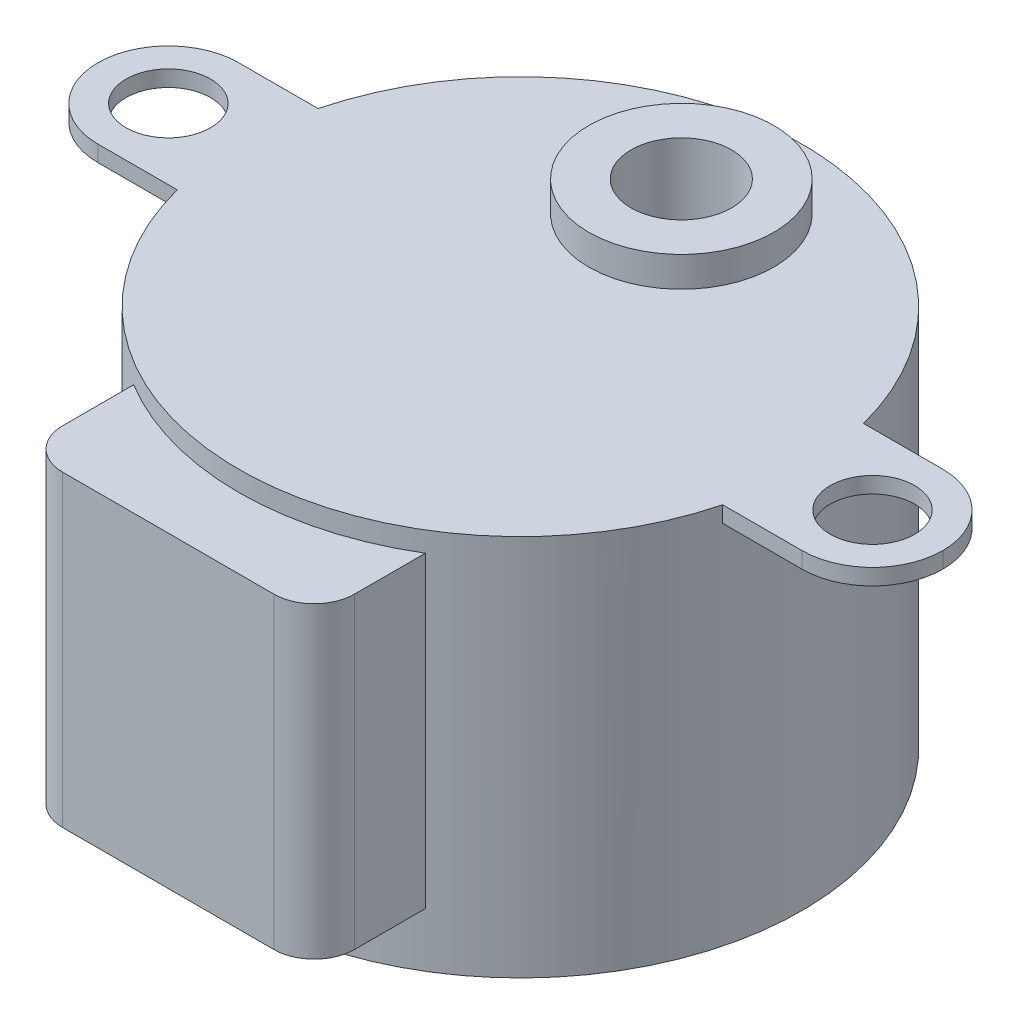
SolidWorks part; units mm, degrees
ref_plane "Plan de face" through (0, 0, 0) normal (0, 0, 1) x (1, 0, 0)
ref_plane "Plan de dessus" through (0, 0, 0) normal (0, 1, 0) x (1, 0, 0)
ref_plane "Plan de droite" through (0, 0, 0) normal (1, 0, 0) x (0, 0, -1)
sketch "Esquisse1" plane through (0, 0, 0) normal (0, 1, 0) x (1, 0, 0)
  circle A0 centre (0, 0) radius 14
  dimension "D1" = 28
extrude "Boss.-Extru.1" add sketch "Esquisse1" along normal blind 19
sketch "Esquisse2" plane through (0, 19, 0) normal (0, 1, 0) x (1, 0, 0)
  line L0 (0, 0) -> (-28.1489, 0) construction
  line L2 (-21, 3.5) -> (21, 3.5)
  line L3 (-21, 3.5) -> (-21, -3.5)
  line L4 (-21, -3.5) -> (21, -3.5)
  line L5 (21, 3.5) -> (21, -3.5)
  circle A0 centre (-17.5, 0) radius 2.1
  circle A1 centre (17.5, 0) radius 2.1
  dimension "D3" = 4.2
  dimension "D4" = 4.2
  dimension "D1" = 21
  dimension "D2" = 21
  dimension "D5" = 17.5
  dimension "D6" = 17.5
  dimension "D7" = 7
  dimension "D8" = 3.5
extrude "Boss.-Extru.2" add sketch "Esquisse2" against normal blind 0.8
fillet "Congé1" radius 3.5 4 edges at (21, 18.6, 3.5) (21, 18.6, -3.5) (-21, 18.6, 3.5) (-21, 18.6, -3.5)
sketch "Esquisse3" plane through (0, 19, 0) normal (0, 1, 0) x (1, 0, 0)
  line L1 (-7.25, -9.5) -> (7.25, -9.5)
  line L2 (-7.25, -9.5) -> (-7.25, -17.5)
  line L3 (-7.25, -17.5) -> (7.25, -17.5)
  line L4 (7.25, -9.5) -> (7.25, -17.5)
  dimension "D1" = 17.5
  dimension "D2" = 7.25
  dimension "D3" = 14.5
  dimension "D4" = 8
extrude "Boss.-Extru.3" add sketch "Esquisse3" against normal blind 16.3
fillet "Congé2" radius 2 2 edges at (-7.25, 10.85, 17.5) (7.25, 10.85, 17.5)
sketch "Esquisse4" plane through (0, 19, 0) normal (0, 1, 0) x (1, 0, 0)
  line L0 (0, 0) -> (0, 13.4825) construction
  circle A0 centre (0, 8) radius 4.6
  dimension "D2" = 9.2
  dimension "D1" = 8
extrude "Boss.-Extru.4" add sketch "Esquisse4" along normal blind 1.5
sketch "Esquisse5" plane through (0, 20.5, 0) normal (0, 1, 0) x (1, 0, 0)
  circle A0 centre (0, 8) radius 2.5
  dimension "D1" = 5
extrude "Boss.-Extru.5" add sketch "Esquisse5" along normal blind 8.5
sketch "Esquisse6" plane through (0, 29, 0) normal (0, 1, 0) x (1, 0, 0)
  line L1 (-6.224, 13.9551) -> (6.4206, 13.9551)
  line L2 (-6.224, 13.9551) -> (-6.224, 9.5)
  line L3 (-6.224, 9.5) -> (6.4206, 9.5)
  line L4 (6.4206, 13.9551) -> (6.4206, 9.5)
  line L5 (-7.4689, 1.7173) -> (7.5999, 1.7173)
  line L6 (-7.4689, 1.7173) -> (-7.4689, 6.5)
  line L7 (-7.4689, 6.5) -> (7.5999, 6.5)
  line L8 (7.5999, 1.7173) -> (7.5999, 6.5)
  circle A0 centre (0, 8) radius 2.5 construction
  dimension "D1" = 1.5
  dimension "D2" = 1.5
extrude "Enlèv. mat.-Extru.1" cut sketch "Esquisse6" against normal blind 6
sketch "Esquisse7" plane through (0, 19, 0) normal (0, 1, 0) x (1, 0, 0)
  line L0 (-7.25, -11.9765) -> (-7.25, -22.1692)
  line L1 (-7.25, -22.1692) -> (7.25, -22.1692)
  line L2 (7.25, -22.1692) -> (7.25, -11.9765)
  arc A0 (-7.25, -11.9765) -> (7.25, -11.9765) centre (0, 0) ccw
extrude "Enlèv. mat.-Extru.2" cut sketch "Esquisse7" against normal blind 1
sketch "Esquisse8" plane through (0, 29, 0) normal (0, 1, 0) x (1, 0, 0)
  circle A0 centre (0, 8) radius 2.5
extrude "Enlèv. mat.-Extru.3" cut sketch "Esquisse8" against normal blind 18.5
sketch "Esquisse11" plane through (0, 0, 17.5) normal (0, 0, 1) x (1, 0, 0)
  line L0 (-17.0489, 18.2) -> (-10.3037, 18.2)
  line L1 (-17.5, 18.2) -> (-13.5554, 18.2) construction
  line L2 (-1.9544, 20.5) -> (1.6125, 20.5)
  line L3 (4.6, 20.5) -> (-4.6, 20.5) construction
  line L4 (2.5, 20.5) -> (-2.5, 20.5) construction
  line L5 (-14, 0) -> (14, 0) construction
  line L6 (-13.4393, 0) -> (-7.9073, 0)
  dimension "D1" = 2.3
